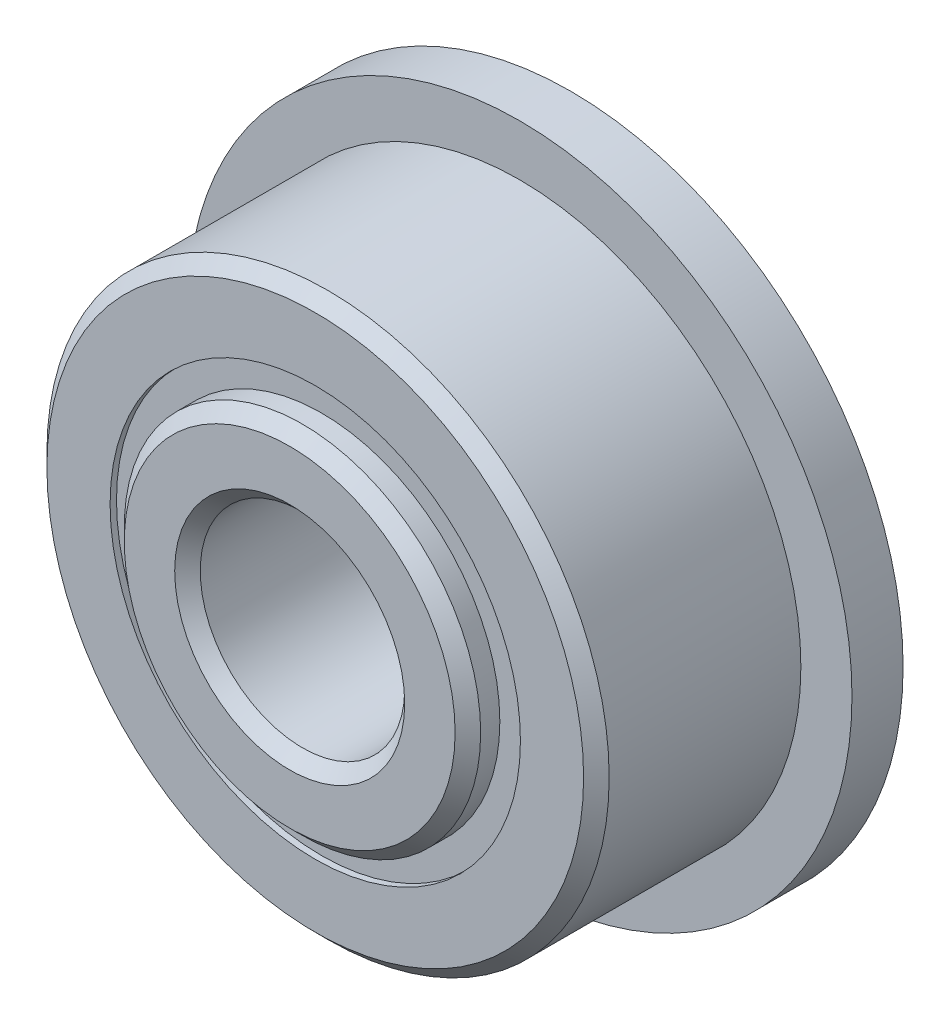
SolidWorks part; units mm, degrees
ref_plane "Front Plane" through (0, 0, 0) normal (0, 0, 1) x (1, 0, 0)
ref_plane "Top Plane" through (0, 0, 0) normal (0, 1, 0) x (1, 0, 0)
ref_plane "Right Plane" through (0, 0, 0) normal (1, 0, 0) x (0, 0, -1)
sketch "Sketch1" plane through (0, 0, 0) normal (1, 0, 0) x (0, 0, -1)
  line L0 (-3.9688, 0) -> (3.9688, 0) construction
  line L1 (0, 8.7312) -> (0, -8.7312) construction
  line L2 (3.5719, 8.7312) -> (-3.5719, 8.7312)
  line L3 (-3.5719, 8.7312) -> (-3.9688, 8.3344)
  line L4 (-3.9688, 8.3344) -> (-3.9688, 6.3718)
  line L5 (-3.9688, 6.3718) -> (-1.7639, 6.3718)
  line L6 (3.9688, 6.3718) -> (1.7639, 6.3718)
  line L7 (3.9688, 8.3344) -> (3.9688, 6.3718)
  line L8 (3.5719, 8.7312) -> (3.9688, 8.3344)
  line L9 (0, 8.7312) -> (0, 5.9531) construction
  line L10 (0, 5.9531) -> (0, 3.175) construction
  arc A0 (-1.7639, 6.3718) -> (1.7639, 6.3718) centre (0, 5.9531) cw
  point P14 (0, 3.175)
  dimension "Width" = 7.9375
  dimension "OD" = 17.4625
  dimension "D1" = 45
  dimension "D2" = 0.3969
  dimension "D3" = 3.5278
  dimension "D4" = 0.4187
revolve "Revolve1" add sketch "Sketch1" angle 360 about L0
sketch "Sketch3" plane through (0, 0, 0) normal (1, 0, 0) x (0, 0, -1)
  line L0 (-1.7639, 5.5344) -> (-4.7625, 5.5344) construction
  line L1 (-3.9688, 8.3344) -> (-3.9688, 6.3718) construction
  line L2 (-3.5719, 8.7312) -> (-3.9688, 8.3344) construction
  line L3 (-4.7625, 5.5344) -> (-4.7625, 3.5719) construction
  line L4 (-4.7625, 3.5719) -> (-4.7625, 5.1376)
  line L5 (-4.7625, 3.5719) -> (-4.3656, 3.175)
  line L6 (-4.3656, 3.175) -> (4.3656, 3.175)
  line L8 (4.3656, 3.175) -> (4.7625, 3.5719)
  line L10 (4.7625, 3.5719) -> (4.7625, 5.5344) construction
  line L11 (4.7625, 5.5344) -> (1.7639, 5.5344) construction
  line L12 (0, 8.7312) -> (0, -8.7312) construction
  line L13 (3.5719, 8.7312) -> (3.9688, 8.3344) construction
  line L14 (-4.7625, 5.1376) -> (-4.3656, 5.5344)
  line L15 (-4.3656, 5.5344) -> (-1.7639, 5.5344)
  line L16 (1.7639, 5.5344) -> (4.3656, 5.5344)
  line L17 (4.3656, 5.5344) -> (4.7625, 5.1376)
  line L18 (4.7625, 5.1376) -> (4.7625, 3.5719)
  arc A1 (1.7639, 5.5344) -> (-1.7639, 5.5344) centre (0, 5.9531) cw
  arc A2 (1.7639, 6.3718) -> (-1.7639, 6.3718) centre (0, 5.9531) ccw construction
  dimension "D1" = 45
  dimension "Ring Wd" = 9.525
revolve "Revolve3" add sketch "Sketch3" angle 360 about L0
sketch "Sketch4" plane through (0, 0, 0) normal (1, 0, 0) x (0, 0, -1)
  line L0 (-1.8129, 5.9531) -> (1.8129, 5.9531)
  arc A2 (-1.8129, 5.9531) -> (1.8129, 5.9531) centre (0, 5.9531) cw
  arc A3 (1.7639, 6.3718) -> (-1.7639, 6.3718) centre (0, 5.9531) ccw construction
revolve "Revolve4" add sketch "Sketch4" angle 360 about L0
ref_axis "Axis1" through (0, 0, -3.9688) along (0, 0, 1)
pattern_circular "CirPattern1" count 10 every 36 about axis through (0, 0, -3.9688) along (0, 0, 1) of bodies 104
sketch "Sketch5" plane through (0, 0, 0) normal (1, 0, 0) x (0, 0, -1)
  line L0 (-3.9688, 6.3718) -> (-1.7639, 6.3718) construction
  line L1 (-3.7703, 6.3718) -> (-1.8129, 6.3718)
  line L2 (-3.7703, 6.3718) -> (-3.7703, 5.5344)
  line L3 (-3.7703, 5.5344) -> (-1.8129, 5.5344)
  line L4 (-1.8129, 6.3718) -> (-1.8129, 5.5344)
  line L5 (-1.7639, 5.5344) -> (-4.7625, 5.5344) construction
  line L6 (3.9688, 6.3718) -> (1.7639, 6.3718) construction
  line L7 (3.7703, 6.3718) -> (1.8129, 6.3718)
  line L8 (3.7703, 6.3718) -> (3.7703, 5.5344)
  line L9 (3.7703, 5.5344) -> (1.8129, 5.5344)
  line L10 (1.8129, 6.3718) -> (1.8129, 5.5344)
  line L11 (4.7625, 5.5344) -> (1.7639, 5.5344) construction
  line L12 (-3.5719, 8.7312) -> (-3.9688, 8.3344) construction
  point P18 (-3.7703, 8.5328)
revolve "Revolve5" add sketch "Sketch5" angle 360 about L0
sketch "Sketch6" plane through (0, 0, 0) normal (1, 0, 0) x (0, 0, -1)
  line L1 (3.9688, 6.3718) -> (2.3813, 6.3718)
  line L2 (3.9688, 6.3718) -> (3.9688, 10.3187)
  line L3 (3.9688, 10.3187) -> (2.3813, 10.3187)
  line L4 (2.3813, 6.3718) -> (2.3813, 10.3187)
  line L5 (3.9688, 0) -> (-3.9688, 0) construction
  dimension "Flange OD" = 20.6375
  dimension "Th" = 1.5875
revolve "Revolve6" add sketch "Sketch6" angle 360 about L5
equation "\"D2@Sketch1\" = \"Width@Sketch1\"*.05"
equation "\"D3@Sketch1\" = \"Width@Sketch1\"/2.25"
equation "\"D4@Sketch1\" = (((\"OD@Sketch1\"-\"Width@Sketch1\")/2)/3.25)/3.5"
equation "\"D2@CirPattern1\" = 360/\"Balls@CirPattern1\""
